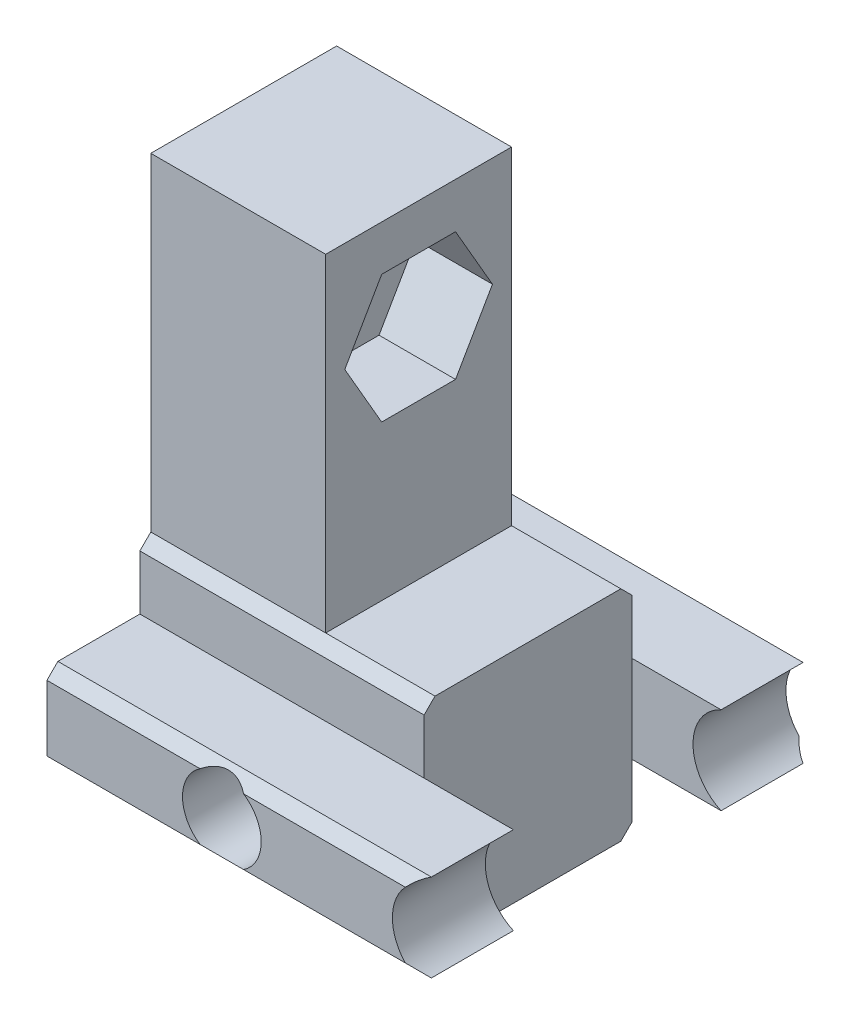
SolidWorks part; units mm, degrees
ref_plane "Front Plane" through (0, 0, 0) normal (0, 0, 1) x (1, 0, 0)
ref_plane "Top Plane" through (0, 0, 0) normal (0, 1, 0) x (1, 0, 0)
ref_plane "Right Plane" through (0, 0, 0) normal (1, 0, 0) x (0, 0, -1)
sketch "Sketch1" plane through (0, 0, 0) normal (0, 0, 1) x (1, 0, 0)
  line L0 (-0.9165, 2) -> (-50, 2)
  line L1 (-50, 2) -> (-50, -2)
  line L3 (-50, -2) -> (-0.9165, -2)
  arc A0 (-0.9165, 2) -> (-0.9165, -2) centre (0, 0) ccw
  dimension "D2" = 4
  dimension "D1" = 2.2
  dimension "D3" = 2
  dimension "D4" = 50
extrude "Boss-Extrude1" add sketch "Sketch1" along normal blind 18
sketch "Sketch2" plane through (-50, 0, 0) normal (-1, 0, 0) x (0, 0, 1)
  line L1 (4.25, 5) -> (13.75, 5)
  line L2 (4.25, 5) -> (4.25, -5)
  line L3 (4.25, -5) -> (13.75, -5)
  line L4 (13.75, 5) -> (13.75, -5)
  line L6 (18, 2) -> (18, -2) construction
  line L7 (18, 2) -> (0, 2) construction
  point P4 (4.25, 0)
  point P7 (18, 0)
  point P8 (9, 5)
  point P11 (9, 2)
  dimension "D1" = 9.5
  dimension "D3" = 10
extrude "Boss-Extrude2" add sketch "Sketch2" against normal up to vertex (49.0835 mm away) up to point (-0.9165, 2, 0)
sketch "Sketch3" plane through (0, 2, 0) normal (0, 1, 0) x (1, 0, 0)
  line L1 (-0.9165, -4.25) -> (4.0835, -4.25)
  line L2 (-0.9165, -4.25) -> (-0.9165, -13.75)
  line L3 (-0.9165, -13.75) -> (4.0835, -13.75)
  line L4 (4.0835, -4.25) -> (4.0835, -13.75)
  dimension "D1" = 9.5
  dimension "D2" = 5
sketch "Sketch4" plane through (0, 0, 18) normal (0, 0, 1) x (1, 0, 0)
  line L0 (-0.9165, 2) -> (-50, 2) construction
  point P0 (-10, 0)
  dimension "D1" = 10
  dimension "D2" = 2
hole_wizard "M3 Clearance Hole1" positions "Sketch5" profile "Sketch6" hole size "M3" standard "DIN" end condition through all
sketch "Sketch5" plane through (0, 0, 18) normal (0, 0, 1) x (1, 0, 0)
  point P0 (-10, 0)
sketch "Sketch6" plane through (-10, 0, 18) normal (1, 0, 0) x (0, -1, 0)
  line L0 (0, 0) -> (0, 18)
  line L1 (0, 18) -> (1.8, 18)
  line L2 (1.8, 18) -> (1.8, 0)
  line L5 (1.8, 0) -> (0, 0)
  line L11 (0, -6.35) -> (0, 107.95) construction
  dimension "Thru Hole Dia." = 3.6
  dimension "Thru Hole Depth" = 18
sketch "Sketch7" plane through (-50, 0, 0) normal (-1, 0, 0) x (0, 0, 1)
  line L0 (0, 2) -> (0, -2)
  line L1 (0, -2) -> (4.25, -2)
  line L2 (4.25, -2) -> (4.25, -5)
  line L3 (4.25, -5) -> (13.75, -5)
  line L4 (13.75, -5) -> (13.75, -2)
  line L5 (13.75, -2) -> (18, -2)
  line L6 (18, -2) -> (18, 2)
  line L7 (18, 2) -> (13.75, 2)
  line L8 (13.75, 2) -> (13.75, 5)
  line L9 (13.75, 5) -> (4.25, 5)
  line L10 (4.25, 5) -> (4.25, 2)
  line L11 (4.25, 2) -> (0, 2)
extrude "Boss-Extrude3" add sketch "Sketch7" along normal blind 1.5
chamfer "Chamfer1" distance 0.5 angle 45 8 edges at (-26.2083, -5, 4.25) (-26.2083, -5, 13.75) (-26.2083, 5, 13.75) (-26.2083, 5, 4.25) (-26.2083, -2, 0) (-26.2083, 2, 0) (-26.2083, -2, 18) (-26.2083, 2, 18)
sketch "Sketch8" plane through (0, 5, 0) normal (0, 1, 0) x (1, 0, 0)
  line L0 (-51.5, -4.25) -> (-0.9165, -4.25) construction
  line L1 (0, -4.25) -> (-5, -4.25)
  line L2 (0, -4.25) -> (0, -13.75)
  line L3 (0, -13.75) -> (-5, -13.75)
  line L4 (-5, -4.25) -> (-5, -13.75)
  line L5 (-0.9165, -13.75) -> (-51.5, -13.75) construction
  dimension "D1" = 5
extrude "Cut-Extrude1" cut sketch "Sketch8" against normal through all
sketch "Sketch9" plane through (0, 5, 0) normal (0, 1, 0) x (1, 0, 0)
  line L0 (-5, -4.75) -> (-51.5, -4.75) construction
  line L1 (-10, -4.75) -> (-18, -4.75)
  line L2 (-10, -4.75) -> (-10, -13.25)
  line L3 (-10, -13.25) -> (-18, -13.25)
  line L4 (-18, -4.75) -> (-18, -13.25)
  line L5 (-51.5, -13.25) -> (-5, -13.25) construction
  line L6 (-5, -4.75) -> (-5, -13.25) construction
  line L8 (0, 0) -> (0, -18.6346) construction
  dimension "D1" = 5
  dimension "D2" = 18
extrude "Boss-Extrude4" add sketch "Sketch9" along normal blind 15
sketch "Sketch10" plane through (-18, 0, 0) normal (-1, 0, 0) x (0, 0, 1)
  line L1 (4.75, 5) -> (13.25, 5) construction
  line L2 (4.75, 20) -> (13.25, 20) construction
  circle A0 centre (9, 15) radius 1.7
  point P7 (9, 20)
  dimension "D1" = 3.4
  dimension "D2" = 10
extrude "Cut-Extrude2" cut sketch "Sketch10" against normal blind 10
sketch "Sketch11" plane through (-10, 0, 0) normal (1, 0, 0) x (0, 0, -1)
  line L0 (-13.25, 20) -> (-4.75, 20) construction
  line L1 (-5.6225, 15) -> (-7.3113, 17.925)
  line L2 (-7.3113, 17.925) -> (-10.6887, 17.925)
  line L3 (-10.6887, 17.925) -> (-12.3775, 15)
  line L4 (-12.3775, 15) -> (-10.6887, 12.075)
  line L5 (-10.6887, 12.075) -> (-7.3113, 12.075)
  line L6 (-7.3113, 12.075) -> (-5.6225, 15)
  circle A0 centre (-9, 15) radius 2.925 construction
  dimension "D1" = 5.85
extrude "Cut-Extrude3" cut sketch "Sketch11" against normal blind 3.5
sketch "Sketch12" plane through (-18, 0, 0) normal (-1, 0, 0) x (0, 0, 1)
  circle A0 centre (9, 15) radius 3.25
  dimension "D1" = 6.5
sketch "Sketch13" plane through (0, 20, 0) normal (0, 1, 0) x (1, 0, 0)
  line L0 (-18, -4.75) -> (-18, -13.25) construction
  line L1 (-51.5, 0) -> (-18, 0)
  line L2 (-51.5, 0) -> (-51.5, -18)
  line L3 (-51.5, -18) -> (-18, -18)
  line L4 (-18, 0) -> (-18, -18)
  line L5 (-10.995, -18) -> (-51.5, -18) construction
  line L6 (-51.5, 0) -> (-10.995, 0) construction
  line L7 (-51.5, -13.25) -> (-51.5, -4.75) construction
extrude "Cut-Extrude5" cut sketch "Sketch13" against normal through all
chamfer "Chamfer2" distance 0.5 angle 45 1 edges at (-18, 15, 10.7)
